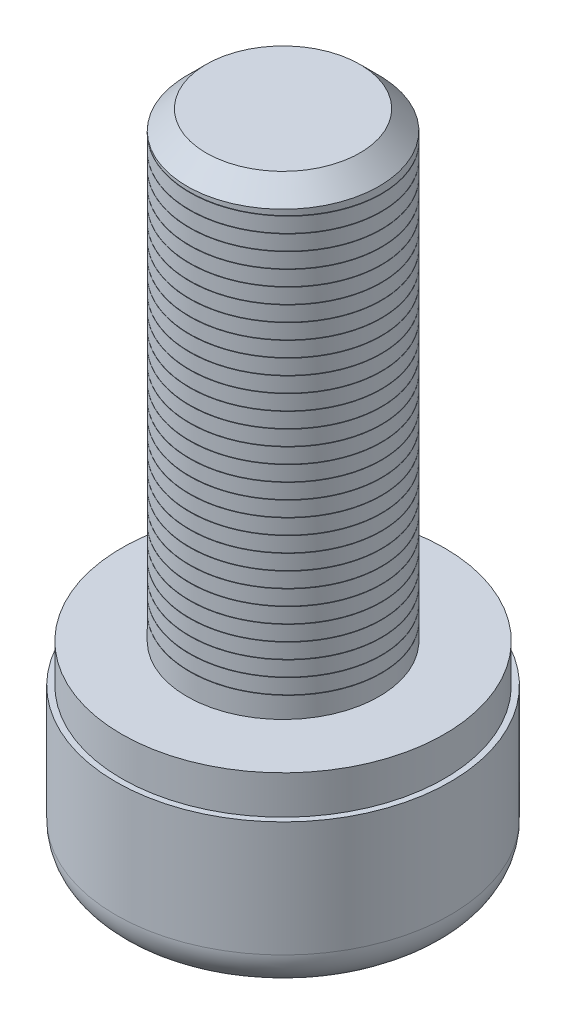
SolidWorks part; units mm, degrees
ref_plane "Спереди" through (0, 0, 0) normal (0, 0, 1) x (1, 0, 0)
ref_plane "Сверху" through (0, 0, 0) normal (0, 1, 0) x (1, 0, 0)
ref_plane "Справа" through (0, 0, 0) normal (1, 0, 0) x (0, 0, -1)
sketch "Эскиз1" plane through (0, 0, 0) normal (0, 1, 0) x (1, 0, 0)
  circle A0 centre (0, 0) radius 4.35
  dimension "D1" = 8.7
extrude "Бобышка-Вытянуть1" add sketch "Эскиз1" along normal blind 5
sketch "Эскиз2" plane through (0, 5, 0) normal (0, 1, 0) x (1, 0, 0)
  circle A0 centre (0, 0) radius 2.5
  dimension "D1" = 5
extrude "Бобышка-Вытянуть2" add sketch "Эскиз2" along normal blind 12
chamfer "Фаска1" distance 0.5 angle 45 1 edges at (0, 17, 2.5)
sketch "Эскиз3" plane through (0, 0, 0) normal (0, -1, 0) x (1, 0, 0)
  line L1 (1.9892, -1.1731) -> (2.0106, 1.1362)
  line L2 (2.0106, 1.1362) -> (0.0214, 2.3093)
  line L3 (0.0214, 2.3093) -> (-1.9892, 1.1731)
  line L4 (-1.9892, 1.1731) -> (-2.0106, -1.1362)
  line L5 (-2.0106, -1.1362) -> (-0.0214, -2.3093)
  line L6 (-0.0214, -2.3093) -> (1.9892, -1.1731)
  circle A0 centre (0, 0) radius 2 construction
  dimension "D1" = 4
extrude "Вырез-Вытянуть1" cut sketch "Эскиз3" against normal blind 2.5
fillet "Скругление1" radius 1 1 edges at (0, 0, 4.35)
sketch "Эскиз4" plane through (0, 5, 0) normal (0, 1, 0) x (1, 0, 0)
  circle A0 centre (0, 0) radius 4.2
  circle A1 centre (0, 0) radius 4.35
  dimension "D1" = 8.4
extrude "Вырез-Вытянуть3" cut sketch "Эскиз4" against normal blind 1
sketch "Эскиз7" plane through (0, 17, 0) normal (0, 1, 0) x (1, 0, 0)
  circle A0 centre (0, 0) radius 2.5
ref_plane "Плоскость2" through (0, 16.5, 0) normal (0, -1, 0) x (-1, 0, 0)
sketch "Эскиз8" plane through (0, 16.5, 0) normal (0, -1, 0) x (-1, 0, 0)
  circle A0 centre (0, 0) radius 2.5
curve "Спираль2" pitch 0.4 height 11.2 radius 2.5 left hand yes centre (0, 16.5, 0) axis (0, -1, 0) start towards (1, 0, 0)
sketch "Эскиз9" plane through (0, 16.5, 0) normal (0, -1, 0) x (-1, 0, 0)
  line L0 (2.6196, 0.3) -> (2.6196, -0.3)
  line L1 (2.6196, -0.3) -> (2.1, 0)
  line L2 (2.1, 0) -> (2.6196, 0.3)
  circle A0 centre (0, 0) radius 2.5 construction
  point P0 (2.5, 0)
  dimension "D1" = 0.6
  dimension "D2" = 0.4
sweep "Вырез-По траектории1" cut profiles "Эскиз9" path "Спираль2"
